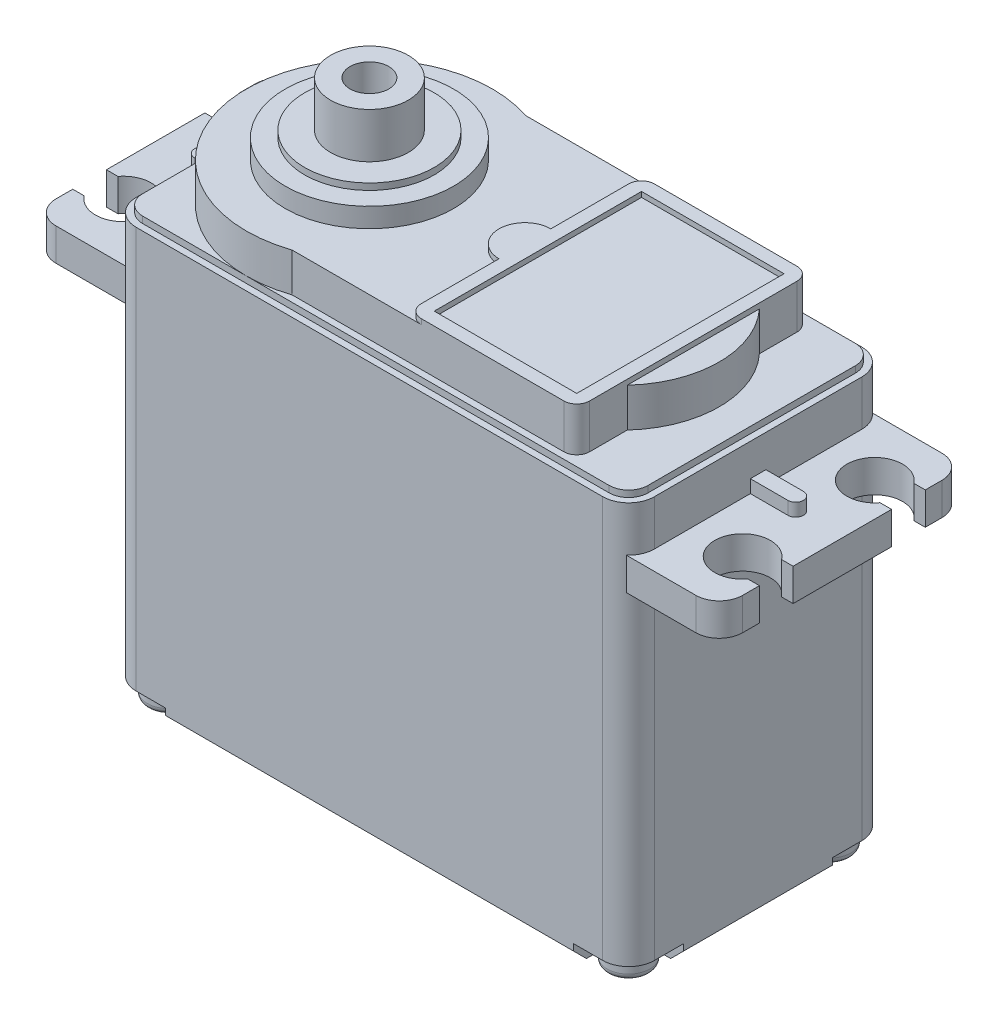
SolidWorks part; units mm, degrees
ref_plane "Спереди" through (0, 0, 0) normal (0, 0, 1) x (1, 0, 0)
ref_plane "Сверху" through (0, 0, 0) normal (0, 1, 0) x (1, 0, 0)
ref_plane "Справа" through (0, 0, 0) normal (1, 0, 0) x (0, 0, -1)
sketch "Эскиз1" plane through (0, 0, 0) normal (0, 1, 0) x (1, 0, 0)
  line L1 (-18, -10) -> (18, -10)
  line L2 (-20, -8) -> (-20, 8)
  line L3 (-18, 10) -> (18, 10)
  line L4 (20, -8) -> (20, 8)
  line L5 (-20, -10) -> (20, 10) construction
  line L6 (-20, 10) -> (20, -10) construction
  arc A0 (-18, -10) -> (-20, -8) centre (-18, -8) cw
  arc A1 (20, -8) -> (18, -10) centre (18, -8) cw
  arc A2 (20, 8) -> (18, 10) centre (18, 8) ccw
  arc A3 (-20, 8) -> (-18, 10) centre (-18, 8) cw
  point P0 (0, 0)
  dimension "D3" = 2
  dimension "D1" = 20
  dimension "D2" = 40
extrude "Бобышка-Вытянуть1" add sketch "Эскиз1" along normal blind 32.5
sketch "Эскиз2" plane through (0, 32.5, 0) normal (0, 1, 0) x (1, 0, 0)
  line L12 (-18, -9.5) -> (18, -9.5)
  line L13 (19.5, -8) -> (19.5, 8)
  line L14 (18, 9.5) -> (-18, 9.5)
  line L15 (-19.5, 8) -> (-19.5, -8)
  line L16 (-18, -9.5) -> (18, -9.5)
  line L17 (19.5, -8) -> (19.5, 8)
  line L18 (18, 9.5) -> (-18, 9.5)
  line L19 (-19.5, 8) -> (-19.5, -8)
  arc A10 (-19.5, -8) -> (-18, -9.5) centre (-18, -8) ccw
  arc A11 (18, -9.5) -> (19.5, -8) centre (18, -8) ccw
  arc A12 (19.5, 8) -> (18, 9.5) centre (18, 8) ccw
  arc A13 (-18, 9.5) -> (-19.5, 8) centre (-18, 8) ccw
  arc A14 (-19.5, -8) -> (-18, -9.5) centre (-18, -8) ccw
  arc A15 (18, -9.5) -> (19.5, -8) centre (18, -8) ccw
  arc A16 (19.5, 8) -> (18, 9.5) centre (18, 8) ccw
  arc A17 (-18, 9.5) -> (-19.5, 8) centre (-18, 8) ccw
  dimension "D1" = 0.5
extrude "Бобышка-Вытянуть2" add sketch "Эскиз2" along normal blind 0.5
sketch "Эскиз3" plane through (0, 0, 0) normal (0, -1, 0) x (1, 0, 0)
  line L0 (-21.9185, 5.75) -> (-17.75, 5.75)
  line L1 (-15.75, 7.75) -> (-15.75, 12.0926)
  line L2 (-20, -8) -> (-20, 8) construction
  line L3 (-18, 10) -> (18, 10) construction
  line L4 (-21.9185, 5.75) -> (-21.9185, 12.0926)
  line L6 (-15.75, 12.0926) -> (-21.9185, 12.0926)
  line L8 (15.75, 12.0926) -> (21.9185, 12.0926)
  line L9 (21.9185, 5.75) -> (21.9185, 12.0926)
  line L10 (15.75, 7.75) -> (15.75, 12.0926)
  line L11 (21.9185, 5.75) -> (17.75, 5.75)
  line L12 (21.9185, -5.75) -> (17.75, -5.75)
  line L13 (15.75, -7.75) -> (15.75, -12.0926)
  line L14 (21.9185, -5.75) -> (21.9185, -12.0926)
  line L15 (15.75, -12.0926) -> (21.9185, -12.0926)
  line L16 (-15.75, -12.0926) -> (-21.9185, -12.0926)
  line L17 (-21.9185, -5.75) -> (-21.9185, -12.0926)
  line L18 (-15.75, -7.75) -> (-15.75, -12.0926)
  line L19 (-21.9185, -5.75) -> (-17.75, -5.75)
  arc A0 (-15.75, 7.75) -> (-17.75, 5.75) centre (-17.75, 7.75) cw
  arc A1 (15.75, 7.75) -> (17.75, 5.75) centre (17.75, 7.75) ccw
  arc A2 (15.75, -7.75) -> (17.75, -5.75) centre (17.75, -7.75) cw
  arc A3 (-15.75, -7.75) -> (-17.75, -5.75) centre (-17.75, -7.75) ccw
  point P11 (-15.75, 5.75)
  point P21 (15.75, 5.75)
  point P34 (15.75, -5.75)
  point P35 (-15.75, -5.75)
  dimension "D3" = 2
  dimension "D1" = 4.25
  dimension "D2" = 4.25
extrude "Вырез-Вытянуть1" cut sketch "Эскиз3" against normal blind 1.5
chamfer "Фаска1" distance 1 angle 45 4 edges at (20, 0, 0) (0, 0, -10) (-20, 0, 0) (0, 0, 10)
sketch "Эскиз4" plane through (0, 33, 0) normal (0, 1, 0) x (1, 0, 0)
  line L1 (18, 9.5) -> (-18, 9.5) construction
  line L2 (-18, -9.5) -> (18, -9.5) construction
  line L3 (-19.5, 8) -> (-19.5, -8) construction
  line L4 (15, 8) -> (15, -8)
  line L5 (20, -8) -> (20, 8) construction
  line L6 (-6.9586, 9) -> (14, 9)
  line L7 (-6.9586, -9) -> (14, -9)
  line L8 (18, 10) -> (-18, 10) construction
  line L9 (-18, -10) -> (18, -10) construction
  arc A0 (-6.9586, 9) -> (-6.9586, -9) centre (-10, 0) ccw
  arc A1 (15, 8) -> (14, 9) centre (14, 8) ccw
  arc A2 (15, -8) -> (14, -9) centre (14, -8) cw
  dimension "D1" = 5
  dimension "D4" = 1
  dimension "D2" = 1
  dimension "D3" = 1
extrude "Бобышка-Вытянуть3" add sketch "Эскиз4" along normal blind 3
sketch "Эскиз5" plane through (0, 36, 0) normal (0, 1, 0) x (1, 0, 0)
  line L0 (15, -8) -> (15, 8) construction
  line L1 (15, -8) -> (15, 8)
  line L2 (2, 8) -> (2, 2)
  line L3 (14, 9) -> (3, 9)
  line L4 (2, -2) -> (2, -8)
  line L5 (14, -9) -> (3, -9)
  line L6 (3, -8) -> (14, -8)
  line L7 (14, 8) -> (3, 8)
  line L8 (3, 8) -> (3, -8)
  line L9 (14, -8) -> (14, 8)
  line L11 (2, 8) -> (2, -8) construction
  arc A0 (15, 8) -> (14, 9) centre (14, 8) ccw construction
  arc A1 (14, -9) -> (15, -8) centre (14, -8) ccw construction
  arc A2 (15, 8) -> (14, 9) centre (14, 8) ccw
  arc A3 (14, -9) -> (15, -8) centre (14, -8) ccw
  arc A4 (3, -9) -> (2, -8) centre (3, -8) cw
  arc A5 (3, 9) -> (2, 8) centre (3, 8) ccw
  arc A6 (2, 2) -> (2, -2) centre (2, 0) ccw
  arc M1 (15, 8) -> (14, 9) centre (14, 8) ccw
  line M2 (14, 9) -> (-6.9586, 9)
  line M4 (-6.9586, -9) -> (14, -9)
  arc M5 (14, -9) -> (15, -8) centre (14, -8) ccw
  line M6 (15, -8) -> (15, 8)
  dimension "D2" = 1
  dimension "D4" = 4
  dimension "D1" = 13
  dimension "D3" = 1
extrude "Бобышка-Вытянуть4" add sketch "Эскиз5" along normal blind 0.4 contours L11 A6 | L2 L11 L4 A4 A5 L9 L6 L8 L7 M4 M5 M6 M1 M2 region at (14.5501, 36, 8.5501) region at (1.1512, 36, 0)
sketch "Эскиз6" plane through (0, 36, 0) normal (0, 1, 0) x (1, 0, 0)
  circle A0 centre (-10, 0) radius 6.5
  dimension "D1" = 13
extrude "Бобышка-Вытянуть5" add sketch "Эскиз6" along normal blind 1.5
sketch "Эскиз7" plane through (0, 37.5, 0) normal (0, 1, 0) x (1, 0, 0)
  circle A0 centre (-10, 0) radius 5
  dimension "D1" = 10
extrude "Бобышка-Вытянуть6" add sketch "Эскиз7" along normal blind 0.5
sketch "Эскиз8" plane through (0, 38, 0) normal (0, 1, 0) x (1, 0, 0)
  circle A0 centre (-10, 0) radius 3
  circle A1 centre (-10, 0) radius 1.5
  dimension "D1" = 6
  dimension "D2" = 3
extrude "Бобышка-Вытянуть7" add sketch "Эскиз8" along normal blind 3.5
sketch "Эскиз9" plane through (0, 33, 0) normal (0, 1, 0) x (1, 0, 0)
  line L1 (20, -8) -> (20, 8) construction
  line L2 (14.5, 5.5902) -> (14.5, -5.5902)
  line L3 (19.5, -8) -> (19.5, 8) construction
  arc A0 (14.5, -5.5902) -> (14.5, 5.5902) centre (9.5, 0) ccw
  dimension "D1" = 15
  dimension "D2" = 10.5
  dimension "D3" = 5
extrude "Бобышка-Вытянуть8" add sketch "Эскиз9" along normal blind 3
ref_plane "Плоскость1" through (0, 26.5, 0) normal (0, -1, 0) x (-1, 0, 0)
sketch "Эскиз10" plane through (0, 26.5, 0) normal (0, -1, 0) x (-1, 0, 0)
  line L0 (-26.5, 6.4) -> (-25.6125, 6.4)
  line L1 (-24.6884, -9.5) -> (24.6884, -9.5)
  line L2 (-26.5, -7.6884) -> (-26.5, -6.4)
  line L3 (-24.6884, 9.5) -> (24.6884, 9.5)
  line L4 (26.5, -7.6884) -> (26.5, -6.4)
  line L5 (-26.5, -9.5) -> (26.5, 9.5) construction
  line L6 (-26.5, 9.5) -> (26.5, -9.5) construction
  line L7 (-26.5, 3.8) -> (-25.6125, 3.8)
  line L8 (-26.5, 6.4) -> (-26.5, 7.6884)
  line L9 (0, 0) -> (-7.7074, 0) construction
  line L10 (-7.7074, 0) -> (0, 0) construction
  line L11 (0, 0) -> (0, 4.5311) construction
  line L12 (26.5, 3.8) -> (25.6125, 3.8)
  line L13 (26.5, 6.4) -> (25.6125, 6.4)
  line L14 (26.5, 6.4) -> (26.5, 7.6884)
  line L15 (26.5, -3.8) -> (25.6125, -3.8)
  line L16 (26.5, -6.4) -> (25.6125, -6.4)
  line L17 (-26.5, -3.8) -> (-25.6125, -3.8)
  line L18 (-26.5, -6.4) -> (-25.6125, -6.4)
  line L19 (26.5, -3.8) -> (26.5, 3.8)
  line L20 (-26.5, -3.8) -> (-26.5, 3.8)
  arc A0 (26.5, 7.6884) -> (24.6884, 9.5) centre (24.6884, 7.6884) ccw
  arc A1 (26.5, -7.6884) -> (24.6884, -9.5) centre (24.6884, -7.6884) cw
  arc A2 (-24.6884, -9.5) -> (-26.5, -7.6884) centre (-24.6884, -7.6884) cw
  arc A3 (-26.5, 7.6884) -> (-24.6884, 9.5) centre (-24.6884, 7.6884) cw
  arc A4 (-25.6125, 3.8) -> (-25.6125, 6.4) centre (-23.9, 5.1) ccw
  arc A5 (25.6125, 3.8) -> (25.6125, 6.4) centre (23.9, 5.1) cw
  arc A6 (25.6125, -3.8) -> (25.6125, -6.4) centre (23.9, -5.1) ccw
  arc A7 (-25.6125, -3.8) -> (-25.6125, -6.4) centre (-23.9, -5.1) cw
  point P0 (0, 0)
  dimension "D3" = 1.8116
  dimension "D4" = 4.3
  dimension "D1" = 19
  dimension "D2" = 53
  dimension "D5" = 5.1
  dimension "D6" = 23.9
  dimension "D7" = 1.3
  dimension "D8" = 2.6
extrude "Бобышка-Вытянуть9" add sketch "Эскиз10" against normal blind 2.5
sketch "Эскиз11" plane through (0, 29, 0) normal (0, 1, 0) x (1, 0, 0)
  line L0 (26.5, 3.8) -> (26.5, -3.8) construction
  line L1 (22.9, 0.6) -> (18.0276, 0.6)
  line L2 (22.9, -0.6) -> (18.0276, -0.6)
  line L6 (18.0276, -0.6) -> (18.0276, 0.6)
  line L7 (0, 0) -> (0, 3.7247) construction
  line L8 (-22.9, 0.6) -> (-18.0276, 0.6)
  line L9 (-18.0276, -0.6) -> (-18.0276, 0.6)
  line L10 (-22.9, -0.6) -> (-18.0276, -0.6)
  arc A0 (22.9, -0.6) -> (22.9, 0.6) centre (22.9, 0) ccw
  arc A1 (2, 2) -> (2, -2) centre (2, 0) ccw construction
  arc A2 (-22.9, -0.6) -> (-22.9, 0.6) centre (-22.9, 0) cw
  point P4 (26.5, 0)
  dimension "D1" = 1.2
  dimension "D2" = 3.6
extrude "Бобышка-Вытянуть10" add sketch "Эскиз11" along normal blind 1
sketch "Эскиз12" plane through (0, 1.5, 0) normal (0, -1, 0) x (1, 0, 0)
  line L0 (0, 0) -> (0, 4.3916) construction
  line L1 (0, 0) -> (-4.3775, 0) construction
  line L2 (-18, 8) -> (-19, 8)
  line L3 (-19, 8) -> (-19, 7.5)
  line L4 (-19, 7.5) -> (-18, 7.5)
  line L5 (-17.5, 8) -> (-17.5, 9)
  line L6 (-17.5, 9) -> (-18, 9)
  line L7 (-18, 9) -> (-18, 8)
  line L8 (-17.5, 7.5) -> (-16.5, 7.5)
  line L9 (-16.5, 7.5) -> (-16.5, 8)
  line L10 (-16.5, 8) -> (-17.5, 8)
  line L11 (-18, 7.5) -> (-18, 6.5)
  line L12 (-18, 6.5) -> (-17.5, 6.5)
  line L13 (-17.5, 6.5) -> (-17.5, 7.5)
  line L14 (16.5, 7.5) -> (16.5, 8)
  line L15 (17.5, 7.5) -> (16.5, 7.5)
  line L16 (17.5, 6.5) -> (17.5, 7.5)
  line L17 (18, 6.5) -> (17.5, 6.5)
  line L18 (18, 7.5) -> (18, 6.5)
  line L19 (19, 7.5) -> (18, 7.5)
  line L20 (19, 8) -> (19, 7.5)
  line L21 (18, 8) -> (19, 8)
  line L22 (18, 9) -> (18, 8)
  line L23 (17.5, 9) -> (18, 9)
  line L24 (17.5, 8) -> (17.5, 9)
  line L25 (16.5, 8) -> (17.5, 8)
  line L26 (16.5, -8) -> (17.5, -8)
  line L27 (16.5, -7.5) -> (16.5, -8)
  line L28 (17.5, -7.5) -> (16.5, -7.5)
  line L29 (18, -6.5) -> (17.5, -6.5)
  line L30 (17.5, -6.5) -> (17.5, -7.5)
  line L31 (18, -7.5) -> (18, -6.5)
  line L32 (19, -7.5) -> (18, -7.5)
  line L33 (19, -8) -> (19, -7.5)
  line L34 (18, -8) -> (19, -8)
  line L35 (18, -9) -> (18, -8)
  line L36 (17.5, -9) -> (18, -9)
  line L37 (17.5, -8) -> (17.5, -9)
  line L38 (-17.5, -6.5) -> (-17.5, -7.5)
  line L39 (-18, -6.5) -> (-17.5, -6.5)
  line L40 (-18, -7.5) -> (-18, -6.5)
  line L41 (-19, -7.5) -> (-18, -7.5)
  line L42 (-19, -8) -> (-19, -7.5)
  line L43 (-18, -8) -> (-19, -8)
  line L44 (-16.5, -7.5) -> (-16.5, -8)
  line L45 (-17.5, -7.5) -> (-16.5, -7.5)
  line L46 (-16.5, -8) -> (-17.5, -8)
  line L47 (-17.5, -8) -> (-17.5, -9)
  line L48 (-18, -9) -> (-18, -8)
  line L49 (-17.5, -9) -> (-18, -9)
  circle A0 centre (-17.75, 7.75) radius 1.65
  circle A1 centre (17.75, 7.75) radius 1.65
  circle A2 centre (17.75, -7.75) radius 1.65
  circle A3 centre (-17.75, -7.75) radius 1.65
  dimension "D1" = 3.3
  dimension "D2" = 7.75
  dimension "D3" = 17.75
  dimension "D4" = 0.5
  dimension "D5" = 0.25
  dimension "D6" = 1.25
  dimension "D7" = 4
extrude "Бобышка-Вытянуть11" add sketch "Эскиз12" along normal blind 1.5
fillet "Скругление1" radius 0.5 4 edges at (17.75, 0, 9.4) (17.75, 0, -9.4) (-17.75, 0, -6.1) (-17.75, 0, 6.1)
ref_plane "Plan1" through (0, 0, 0) normal (-1, 0, 0) x (0, 0, 1)
